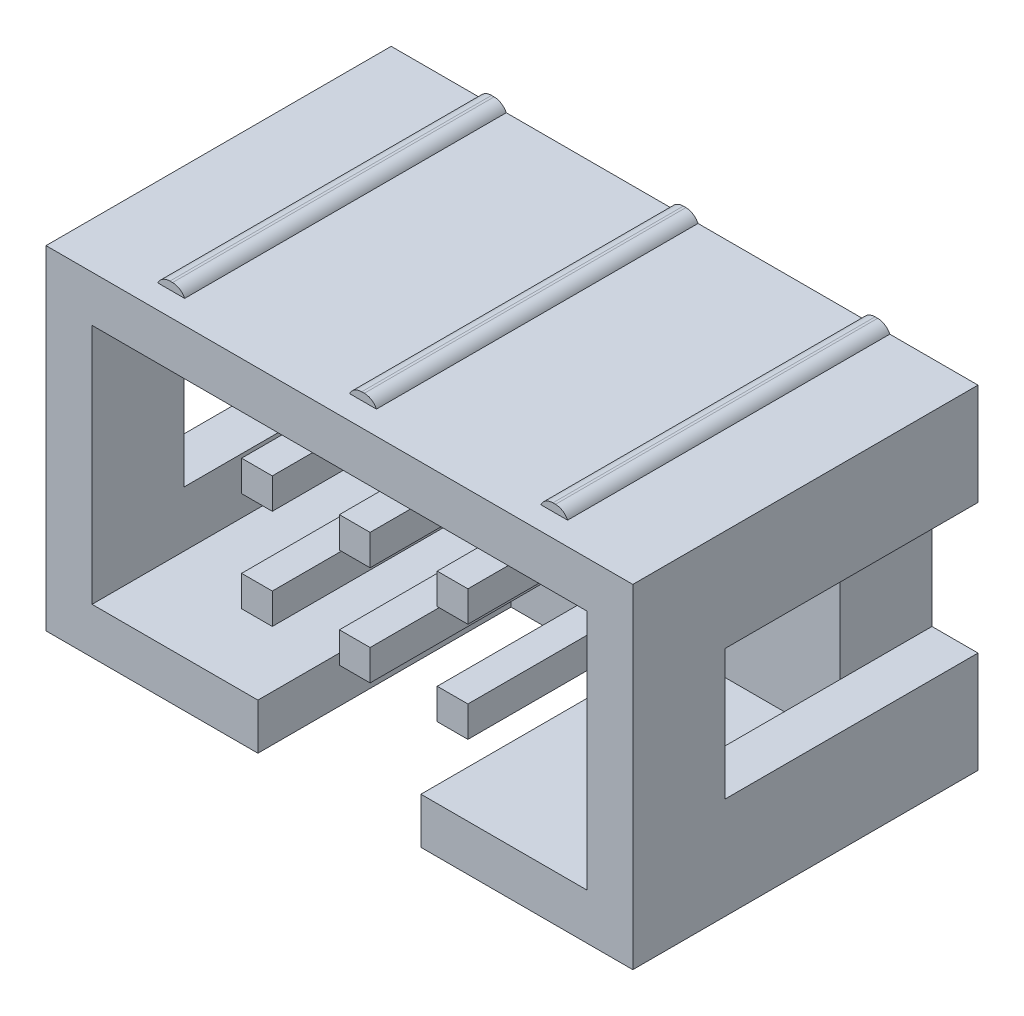
SolidWorks part; units mm, degrees
ref_plane "Přední rovina" through (0, 0, 0) normal (0, 0, 1) x (1, 0, 0)
ref_plane "Horní rovina" through (0, 0, 0) normal (0, 1, 0) x (1, 0, 0)
ref_plane "Pravá rovina" through (0, 0, 0) normal (1, 0, 0) x (0, 0, -1)
sketch "Skica1" plane through (0, 0, 0) normal (0, 0, 1) x (1, 0, 0)
  line L1 (-7.65, -4.35) -> (7.65, -4.35)
  line L2 (-7.65, -4.35) -> (-7.65, 4.35)
  line L3 (-7.65, 4.35) -> (7.65, 4.35)
  line L4 (7.65, -4.35) -> (7.65, 4.35)
  line L5 (-7.65, -4.35) -> (7.65, 4.35) construction
  line L6 (-7.65, 4.35) -> (7.65, -4.35) construction
  point P0 (0, 0)
  dimension "D1" = 15.3
  dimension "D2" = 8.7
extrude "Přidat vysunutím1" add sketch "Skica1" along normal blind 9
sketch "Skica2" plane through (0, 0, 9) normal (0, 0, 1) x (1, 0, 0)
  line L0 (7.65, 4.35) -> (-7.65, 4.35) construction
  line L1 (-6.45, -3.15) -> (6.45, -3.15)
  line L2 (-6.45, -3.15) -> (-6.45, 3.15)
  line L3 (-6.45, 3.15) -> (6.45, 3.15)
  line L4 (6.45, -3.15) -> (6.45, 3.15)
  line L5 (-6.45, -3.15) -> (6.45, 3.15) construction
  line L6 (-6.45, 3.15) -> (6.45, -3.15) construction
  line L7 (-7.65, 4.35) -> (-7.65, -4.35) construction
  point P0 (0, 0)
  dimension "D1" = 1.2
  dimension "D2" = 1.2
extrude "Odebrat vysunutím1" cut sketch "Skica2" against normal blind 6.6
sketch "Skica3" plane through (0, -4.35, 0) normal (0, -1, 0) x (-1, 0, 0)
  line L0 (7.65, -9) -> (-7.65, -9) construction
  line L1 (2.125, -2.4) -> (-2.125, -2.4)
  line L2 (2.125, -2.4) -> (2.125, -9)
  line L3 (2.125, -9) -> (-2.125, -9)
  line L4 (-2.125, -2.4) -> (-2.125, -9)
  line L5 (2.125, -2.4) -> (-2.125, -9) construction
  line L6 (2.125, -9) -> (-2.125, -2.4) construction
  line L8 (0, -9) -> (0, 0) construction
  line L9 (7.65, 0) -> (-7.65, 0) construction
  line L10 (-6.45, -2.4) -> (6.45, -2.4) construction
  line L11 (-6.45, -9) -> (6.45, -9) construction
  point P0 (0, -5.7)
  dimension "D1" = 4.25
  dimension "D2" = 6.6
extrude "Odebrat vysunutím2" cut sketch "Skica3" against normal blind 6.6
sketch "Skica4" plane through (-7.65, 0, 0) normal (-1, 0, 0) x (0, 0, 1)
  line L0 (0, 4.35) -> (0, -4.35) construction
  line L1 (0, 1.7) -> (6.6, 1.7)
  line L2 (0, 1.7) -> (0, -1.7)
  line L3 (0, -1.7) -> (6.6, -1.7)
  line L4 (6.6, 1.7) -> (6.6, -1.7)
  line L5 (9, 0) -> (0, 0) construction
  line L6 (9, 4.35) -> (9, -4.35) construction
  dimension "D1" = 6.6
  dimension "D2" = 3.4
extrude "Odebrat vysunutím3" cut sketch "Skica4" against normal up to vertex (1.2 mm away) up to point (-6.45, -3.15, 9)
sketch "Skica5" plane through (7.65, 0, 0) normal (1, 0, 0) x (0, 0, -1)
  line L0 (0, -4.35) -> (0, 4.35) construction
  line L1 (0, -1.7) -> (-6.6, -1.7)
  line L2 (0, -1.7) -> (0, 1.7)
  line L3 (0, 1.7) -> (-6.6, 1.7)
  line L4 (-6.6, -1.7) -> (-6.6, 1.7)
  line L5 (-9, 0) -> (0, 0) construction
  line L6 (-9, -4.35) -> (-9, 4.35) construction
  dimension "D1" = 3.4
  dimension "D2" = 6.6
extrude "Odebrat vysunutím4" cut sketch "Skica5" against normal up to vertex (1.2 mm away) up to point (6.45, 3.15, 9)
sketch "Skica6" plane through (0, 4.35, 0) normal (0, 1, 0) x (1, 0, 0)
  line L0 (7.65, 0) -> (-7.65, 0) construction
  line L1 (5.35, 0) -> (4.65, 0)
  line L2 (5.35, 0) -> (5.35, -8.4)
  line L3 (5.35, -8.4) -> (4.65, -8.4)
  line L4 (4.65, 0) -> (4.65, -8.4)
  line L5 (7.65, -9) -> (-7.65, -9) construction
  line L6 (-7.65, -9) -> (-7.65, 0) construction
  line L10 (0.35, 0) -> (-0.35, 0)
  line L11 (0.35, 0) -> (0.35, -8.3848)
  line L12 (0.35, -8.3848) -> (-0.35, -8.3848)
  line L13 (-0.35, 0) -> (-0.35, -8.3848)
  line L14 (-4.65, -8.3848) -> (-5.35, -8.3848)
  line L15 (-4.65, -8.3848) -> (-4.65, 0)
  line L16 (-4.65, 0) -> (-5.35, 0)
  line L17 (-5.35, -8.3848) -> (-5.35, 0)
  line L18 (7.65, -9) -> (7.65, 0) construction
  dimension "D1" = 0.6
  dimension "D2" = 0.7
  dimension "D3" = 2.3
  dimension "D4" = 7.3
  dimension "D5" = 2.3
  dimension "D6" = 7.3
extrude "Přidat vysunutím2" add sketch "Skica6" along normal blind 0.2
fillet "Zaoblit2" radius 0.35 1 edges at (5.35, 4.55, 4.2)
fillet "Zaoblit3" radius 0.35 5 edges at (-5.35, 4.55, 4.1924) (-4.65, 4.55, 4.1924) (-0.35, 4.55, 4.1924) (0.35, 4.55, 4.1924) (4.65, 4.55, 4.2)
sketch "Skica7" plane through (0, 0, 2.4) normal (0, 0, 1) x (1, 0, 0)
  line L0 (-6.45, -3.15) -> (-2.125, -3.15) construction
  line L1 (-2.95, -1.7) -> (-2.15, -1.7)
  line L2 (-2.95, -1.7) -> (-2.95, -0.9)
  line L3 (-2.95, -0.9) -> (-2.15, -0.9)
  line L4 (-2.15, -1.7) -> (-2.15, -0.9)
  line L5 (-2.95, -1.7) -> (-2.15, -0.9) construction
  line L6 (-2.95, -0.9) -> (-2.15, -1.7) construction
  line L7 (-2.95, 0.9) -> (-2.15, 0.9)
  line L8 (-2.95, 0.9) -> (-2.95, 1.7)
  line L9 (-2.95, 1.7) -> (-2.15, 1.7)
  line L10 (-2.15, 0.9) -> (-2.15, 1.7)
  line L11 (-2.95, 0.9) -> (-2.15, 1.7) construction
  line L12 (-2.95, 1.7) -> (-2.15, 0.9) construction
  line L13 (-0.4, -1.7) -> (0.4, -1.7)
  line L14 (-0.4, -1.7) -> (-0.4, -0.9)
  line L15 (-0.4, -0.9) -> (0.4, -0.9)
  line L16 (0.4, -1.7) -> (0.4, -0.9)
  line L17 (-0.4, -1.7) -> (0.4, -0.9) construction
  line L18 (-0.4, -0.9) -> (0.4, -1.7) construction
  line L19 (2.15, -1.7) -> (2.95, -1.7)
  line L20 (2.15, -1.7) -> (2.15, -0.9)
  line L21 (2.15, -0.9) -> (2.95, -0.9)
  line L22 (2.95, -1.7) -> (2.95, -0.9)
  line L23 (2.15, -1.7) -> (2.95, -0.9) construction
  line L24 (2.15, -0.9) -> (2.95, -1.7) construction
  line L25 (2.15, 0.9) -> (2.95, 0.9)
  line L26 (2.15, 0.9) -> (2.15, 1.7)
  line L27 (2.15, 1.7) -> (2.95, 1.7)
  line L28 (2.95, 0.9) -> (2.95, 1.7)
  line L29 (2.15, 0.9) -> (2.95, 1.7) construction
  line L30 (2.15, 1.7) -> (2.95, 0.9) construction
  line L31 (-0.4, 0.9) -> (0.4, 0.9)
  line L32 (-0.4, 0.9) -> (-0.4, 1.7)
  line L33 (-0.4, 1.7) -> (0.4, 1.7)
  line L34 (0.4, 0.9) -> (0.4, 1.7)
  line L35 (-0.4, 0.9) -> (0.4, 1.7) construction
  line L36 (-0.4, 1.7) -> (0.4, 0.9) construction
  line L39 (-6.45, 1.7) -> (-6.45, -1.7) construction
  point P0 (-2.55, -1.3)
  point P5 (-2.55, 1.3)
  point P10 (0, -1.3)
  point P15 (2.55, -1.3)
  point P20 (2.55, 1.3)
  point P25 (0, 1.3)
  dimension "D1" = 0.8
  dimension "D2" = 0.8
  dimension "D3" = 1.75
  dimension "D4" = 1.75
  dimension "D5" = 1.8
  dimension "D6" = 1.45
  dimension "D7" = 3.5
extrude "Přidat vysunutím3" add sketch "Skica7" along normal blind 6.2
